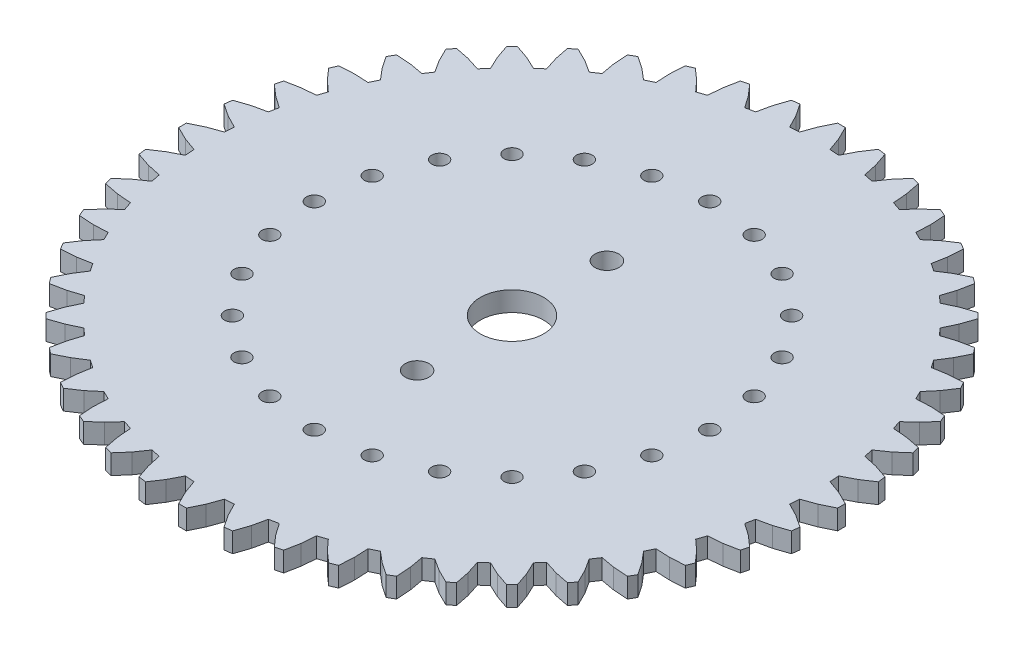
SolidWorks part; units mm, degrees
material "Plain Carbon Steel"
ref_plane "Front Plane" through (0, 0, 0) normal (0, 0, 1) x (1, 0, 0)
ref_plane "Top Plane" through (0, 0, 0) normal (0, 1, 0) x (1, 0, 0)
ref_plane "Right Plane" through (0, 0, 0) normal (1, 0, 0) x (0, 0, -1)
sketch "Sketch5" plane through (0, 0, 0) normal (0, 1, 0) x (1, 0, 0)
  line L0 (87.3464, 51.4964) -> (89.0397, 50.8872)
  line L1 (89.0397, 50.8872) -> (90.7249, 50.062)
  line L2 (90.7249, 50.062) -> (90.7249, 49.095)
  line L3 (90.7249, 49.095) -> (89.0397, 48.2698)
  line L4 (89.0397, 48.2698) -> (87.3464, 47.6606)
  line L5 (87.3464, 47.6606) -> (87.2693, 46.4828)
  line L6 (87.2693, 46.4828) -> (88.8685, 45.6578)
  line L7 (88.8685, 45.6578) -> (90.4317, 44.6196)
  line L8 (90.4317, 44.6196) -> (90.3054, 43.6609)
  line L9 (90.3054, 43.6609) -> (88.5268, 43.0627)
  line L10 (88.5268, 43.0627) -> (86.7686, 42.6797)
  line L11 (86.7686, 42.6797) -> (86.5383, 41.5221)
  line L12 (86.5383, 41.5221) -> (88.0162, 40.4955)
  line L13 (88.0162, 40.4955) -> (89.4304, 39.2621)
  line L14 (89.4304, 39.2621) -> (89.1801, 38.328)
  line L15 (89.1801, 38.328) -> (87.3386, 37.9672)
  line L16 (87.3386, 37.9672) -> (85.5454, 37.8169)
  line L17 (85.5454, 37.8169) -> (85.1661, 36.6994)
  line L18 (85.1661, 36.6994) -> (86.4974, 35.4884)
  line L19 (86.4974, 35.4884) -> (87.7385, 34.0811)
  line L20 (87.7385, 34.0811) -> (87.3685, 33.1877)
  line L21 (87.3685, 33.1877) -> (85.4956, 33.0702)
  line L22 (85.4956, 33.0702) -> (83.6981, 33.1553)
  line L23 (83.6981, 33.1553) -> (83.1762, 32.0968)
  line L24 (83.1762, 32.0968) -> (84.3379, 30.7226)
  line L25 (84.3379, 30.7226) -> (85.3848, 29.1653)
  line L26 (85.3848, 29.1653) -> (84.9013, 28.3278)
  line L27 (84.9013, 28.3278) -> (83.0292, 28.4557)
  line L28 (83.0292, 28.4557) -> (81.2581, 28.7747)
  line L29 (81.2581, 28.7747) -> (80.6024, 27.7935)
  line L30 (80.6024, 27.7935) -> (81.575, 26.2794)
  line L31 (81.575, 26.2794) -> (82.4096, 24.5987)
  line L32 (82.4096, 24.5987) -> (81.821, 23.8315)
  line L33 (81.821, 23.8315) -> (79.9815, 24.2028)
  line L34 (79.9815, 24.2028) -> (78.2673, 24.7502)
  line L35 (78.2673, 24.7502) -> (77.4891, 23.8628)
  line L36 (77.4891, 23.8628) -> (78.2556, 22.2348)
  line L37 (78.2556, 22.2348) -> (78.8638, 20.4595)
  line L38 (78.8638, 20.4595) -> (78.18, 19.7757)
  line L39 (78.18, 19.7757) -> (76.4047, 20.3839)
  line L40 (76.4047, 20.3839) -> (74.7767, 21.1504)
  line L41 (74.7767, 21.1504) -> (73.8893, 20.3722)
  line L42 (73.8893, 20.3722) -> (74.4368, 18.658)
  line L43 (74.4368, 18.658) -> (74.808, 16.8186)
  line L44 (74.808, 16.8186) -> (74.0408, 16.2299)
  line L45 (74.0408, 16.2299) -> (72.3602, 17.0645)
  line L46 (72.3602, 17.0645) -> (70.846, 18.0371)
  line L47 (70.846, 18.0371) -> (69.8648, 17.3814)
  line L48 (69.8648, 17.3814) -> (70.1838, 15.6104)
  line L49 (70.1838, 15.6104) -> (70.3117, 13.7382)
  line L50 (70.3117, 13.7382) -> (69.4742, 13.2547)
  line L51 (69.4742, 13.2547) -> (67.9169, 14.3016)
  line L52 (67.9169, 14.3016) -> (66.5427, 15.4634)
  line L53 (66.5427, 15.4634) -> (65.4842, 14.9415)
  line L54 (65.4842, 14.9415) -> (65.5693, 13.1439)
  line L55 (65.5693, 13.1439) -> (65.4518, 11.271)
  line L56 (65.4518, 11.271) -> (64.5584, 10.901)
  line L57 (64.5584, 10.901) -> (63.1511, 12.1422)
  line L58 (63.1511, 12.1422) -> (61.9401, 13.4734)
  line L59 (61.9401, 13.4734) -> (60.8226, 13.0941)
  line L60 (60.8226, 13.0941) -> (60.6724, 11.3009)
  line L61 (60.6724, 11.3009) -> (60.3115, 9.4594)
  line L62 (60.3115, 9.4594) -> (59.3774, 9.2091)
  line L63 (59.3774, 9.2091) -> (58.144, 10.6233)
  line L64 (58.144, 10.6233) -> (57.1174, 12.1012)
  line L65 (57.1174, 12.1012) -> (55.9598, 11.8709)
  line L66 (55.9598, 11.8709) -> (55.5768, 10.1127)
  line L67 (55.5768, 10.1127) -> (54.9786, 8.3341)
  line L68 (54.9786, 8.3341) -> (54.0199, 8.2078)
  line L69 (54.0199, 8.2078) -> (52.9817, 9.771)
  line L70 (52.9817, 9.771) -> (52.1567, 11.3702)
  line L71 (52.1567, 11.3702) -> (50.979, 11.2931)
  line L72 (50.979, 11.2931) -> (50.3698, 9.5998)
  line L73 (50.3698, 9.5998) -> (49.5446, 7.9146)
  line L74 (49.5446, 7.9146) -> (48.5775, 7.9146)
  line L75 (48.5775, 7.9146) -> (47.7523, 9.5998)
  line L76 (47.7523, 9.5998) -> (47.1431, 11.2931)
  line L77 (47.1431, 11.2931) -> (45.9654, 11.3702)
  line L78 (45.9654, 11.3702) -> (45.1403, 9.771)
  line L79 (45.1403, 9.771) -> (44.1021, 8.2078)
  line L80 (44.1021, 8.2078) -> (43.1434, 8.3341)
  line L81 (43.1434, 8.3341) -> (42.5452, 10.1127)
  line L82 (42.5452, 10.1127) -> (42.1622, 11.8709)
  line L83 (42.1622, 11.8709) -> (41.0046, 12.1012)
  line L84 (41.0046, 12.1012) -> (39.978, 10.6233)
  line L85 (39.978, 10.6233) -> (38.7447, 9.2091)
  line L86 (38.7447, 9.2091) -> (37.8106, 9.4594)
  line L87 (37.8106, 9.4594) -> (37.4497, 11.3009)
  line L88 (37.4497, 11.3009) -> (37.2994, 13.0941)
  line L89 (37.2994, 13.0941) -> (36.1819, 13.4734)
  line L90 (36.1819, 13.4734) -> (34.9709, 12.1422)
  line L91 (34.9709, 12.1422) -> (33.5636, 10.901)
  line L92 (33.5636, 10.901) -> (32.6702, 11.271)
  line L93 (32.6702, 11.271) -> (32.5527, 13.1439)
  line L94 (32.5527, 13.1439) -> (32.6378, 14.9415)
  line L95 (32.6378, 14.9415) -> (31.5793, 15.4634)
  line L96 (31.5793, 15.4634) -> (30.2051, 14.3016)
  line L97 (30.2051, 14.3016) -> (28.6478, 13.2547)
  line L98 (28.6478, 13.2547) -> (27.8103, 13.7382)
  line L99 (27.8103, 13.7382) -> (27.9382, 15.6104)
  line L100 (27.9382, 15.6104) -> (28.2572, 17.3814)
  line L101 (28.2572, 17.3814) -> (27.276, 18.0371)
  line L102 (27.276, 18.0371) -> (25.7619, 17.0645)
  line L103 (25.7619, 17.0645) -> (24.0812, 16.2299)
  line L104 (24.0812, 16.2299) -> (23.314, 16.8186)
  line L105 (23.314, 16.8186) -> (23.6853, 18.658)
  line L106 (23.6853, 18.658) -> (24.2327, 20.3722)
  line L107 (24.2327, 20.3722) -> (23.3453, 21.1504)
  line L108 (23.3453, 21.1504) -> (21.7173, 20.3839)
  line L109 (21.7173, 20.3839) -> (19.9421, 19.7757)
  line L110 (19.9421, 19.7757) -> (19.2582, 20.4595)
  line L111 (19.2582, 20.4595) -> (19.8664, 22.2348)
  line L112 (19.8664, 22.2348) -> (20.6329, 23.8628)
  line L113 (20.6329, 23.8628) -> (19.8547, 24.7502)
  line L114 (19.8547, 24.7502) -> (18.1405, 24.2028)
  line L115 (18.1405, 24.2028) -> (16.3011, 23.8315)
  line L116 (16.3011, 23.8315) -> (15.7124, 24.5987)
  line L117 (15.7124, 24.5987) -> (16.547, 26.2794)
  line L118 (16.547, 26.2794) -> (17.5196, 27.7935)
  line L119 (17.5196, 27.7935) -> (16.8639, 28.7747)
  line L120 (16.8639, 28.7747) -> (15.0929, 28.4557)
  line L121 (15.0929, 28.4557) -> (13.2207, 28.3278)
  line L122 (13.2207, 28.3278) -> (12.7372, 29.1653)
  line L123 (12.7372, 29.1653) -> (13.7841, 30.7226)
  line L124 (13.7841, 30.7226) -> (14.9459, 32.0968)
  line L125 (14.9459, 32.0968) -> (14.424, 33.1553)
  line L126 (14.424, 33.1553) -> (12.6264, 33.0702)
  line L127 (12.6264, 33.0702) -> (10.7535, 33.1877)
  line L128 (10.7535, 33.1877) -> (10.3835, 34.0811)
  line L129 (10.3835, 34.0811) -> (11.6247, 35.4884)
  line L130 (11.6247, 35.4884) -> (12.9559, 36.6994)
  line L131 (12.9559, 36.6994) -> (12.5766, 37.8169)
  line L132 (12.5766, 37.8169) -> (10.7834, 37.9672)
  line L133 (10.7834, 37.9672) -> (8.9419, 38.328)
  line L134 (8.9419, 38.328) -> (8.6916, 39.2621)
  line L135 (8.6916, 39.2621) -> (10.1058, 40.4955)
  line L136 (10.1058, 40.4955) -> (11.5837, 41.5221)
  line L137 (11.5837, 41.5221) -> (11.3534, 42.6797)
  line L138 (11.3534, 42.6797) -> (9.5952, 43.0627)
  line L139 (9.5952, 43.0627) -> (7.8167, 43.6609)
  line L140 (7.8167, 43.6609) -> (7.6903, 44.6196)
  line L141 (7.6903, 44.6196) -> (9.2536, 45.6578)
  line L142 (9.2536, 45.6578) -> (10.8528, 46.4828)
  line L143 (10.8528, 46.4828) -> (10.7757, 47.6606)
  line L144 (10.7757, 47.6606) -> (9.0823, 48.2698)
  line L145 (9.0823, 48.2698) -> (7.3971, 49.095)
  line L146 (7.3971, 49.095) -> (7.3971, 50.062)
  line L147 (7.3971, 50.062) -> (9.0823, 50.8872)
  line L148 (9.0823, 50.8872) -> (10.7757, 51.4964)
  line L149 (10.7757, 51.4964) -> (10.8528, 52.6742)
  line L150 (10.8528, 52.6742) -> (9.2536, 53.4992)
  line L151 (9.2536, 53.4992) -> (7.6903, 54.5374)
  line L152 (7.6903, 54.5374) -> (7.8167, 55.4961)
  line L153 (7.8167, 55.4961) -> (9.5952, 56.0943)
  line L154 (9.5952, 56.0943) -> (11.3534, 56.4773)
  line L155 (11.3534, 56.4773) -> (11.5837, 57.6349)
  line L156 (11.5837, 57.6349) -> (10.1058, 58.6615)
  line L157 (10.1058, 58.6615) -> (8.6916, 59.8949)
  line L158 (8.6916, 59.8949) -> (8.9419, 60.829)
  line L159 (8.9419, 60.829) -> (10.7834, 61.1898)
  line L160 (10.7834, 61.1898) -> (12.5766, 61.3401)
  line L161 (12.5766, 61.3401) -> (12.9559, 62.4576)
  line L162 (12.9559, 62.4576) -> (11.6247, 63.6686)
  line L163 (11.6247, 63.6686) -> (10.3835, 65.0759)
  line L164 (10.3835, 65.0759) -> (10.7535, 65.9693)
  line L165 (10.7535, 65.9693) -> (12.6264, 66.0868)
  line L166 (12.6264, 66.0868) -> (14.424, 66.0017)
  line L167 (14.424, 66.0017) -> (14.9459, 67.0602)
  line L168 (14.9459, 67.0602) -> (13.7841, 68.4344)
  line L169 (13.7841, 68.4344) -> (12.7372, 69.9917)
  line L170 (12.7372, 69.9917) -> (13.2207, 70.8292)
  line L171 (13.2207, 70.8292) -> (15.0929, 70.7013)
  line L172 (15.0929, 70.7013) -> (16.8639, 70.3823)
  line L173 (16.8639, 70.3823) -> (17.5196, 71.3635)
  line L174 (17.5196, 71.3635) -> (16.547, 72.8776)
  line L175 (16.547, 72.8776) -> (15.7124, 74.5583)
  line L176 (15.7124, 74.5583) -> (16.3011, 75.3255)
  line L177 (16.3011, 75.3255) -> (18.1405, 74.9542)
  line L178 (18.1405, 74.9542) -> (19.8547, 74.4068)
  line L179 (19.8547, 74.4068) -> (20.6329, 75.2942)
  line L180 (20.6329, 75.2942) -> (19.8664, 76.9222)
  line L181 (19.8664, 76.9222) -> (19.2582, 78.6975)
  line L182 (19.2582, 78.6975) -> (19.9421, 79.3813)
  line L183 (19.9421, 79.3813) -> (21.7173, 78.7731)
  line L184 (21.7173, 78.7731) -> (23.3453, 78.0066)
  line L185 (23.3453, 78.0066) -> (24.2327, 78.7848)
  line L186 (24.2327, 78.7848) -> (23.6853, 80.499)
  line L187 (23.6853, 80.499) -> (23.314, 82.3384)
  line L188 (23.314, 82.3384) -> (24.0812, 82.9271)
  line L189 (24.0812, 82.9271) -> (25.7619, 82.0925)
  line L190 (25.7619, 82.0925) -> (27.276, 81.1199)
  line L191 (27.276, 81.1199) -> (28.2572, 81.7756)
  line L192 (28.2572, 81.7756) -> (27.9382, 83.5466)
  line L193 (27.9382, 83.5466) -> (27.8103, 85.4188)
  line L194 (27.8103, 85.4188) -> (28.6478, 85.9023)
  line L195 (28.6478, 85.9023) -> (30.2051, 84.8554)
  line L196 (30.2051, 84.8554) -> (31.5793, 83.6936)
  line L197 (31.5793, 83.6936) -> (32.6378, 84.2155)
  line L198 (32.6378, 84.2155) -> (32.5527, 86.0131)
  line L199 (32.5527, 86.0131) -> (32.6702, 87.886)
  line L200 (32.6702, 87.886) -> (33.5636, 88.256)
  line L201 (33.5636, 88.256) -> (34.9709, 87.0148)
  line L202 (34.9709, 87.0148) -> (36.1819, 85.6836)
  line L203 (36.1819, 85.6836) -> (37.2994, 86.0629)
  line L204 (37.2994, 86.0629) -> (37.4497, 87.8561)
  line L205 (37.4497, 87.8561) -> (37.8106, 89.6976)
  line L206 (37.8106, 89.6976) -> (38.7447, 89.9479)
  line L207 (38.7447, 89.9479) -> (39.978, 88.5337)
  line L208 (39.978, 88.5337) -> (41.0046, 87.0558)
  line L209 (41.0046, 87.0558) -> (42.1622, 87.2861)
  line L210 (42.1622, 87.2861) -> (42.5452, 89.0443)
  line L211 (42.5452, 89.0443) -> (43.1434, 90.8228)
  line L212 (43.1434, 90.8228) -> (44.1021, 90.9492)
  line L213 (44.1021, 90.9492) -> (45.1403, 89.386)
  line L214 (45.1403, 89.386) -> (45.9654, 87.7868)
  line L215 (45.9654, 87.7868) -> (47.1431, 87.8639)
  line L216 (47.1431, 87.8639) -> (47.7523, 89.5572)
  line L217 (47.7523, 89.5572) -> (48.5775, 91.2424)
  line L218 (48.5775, 91.2424) -> (49.5446, 91.2424)
  line L219 (49.5446, 91.2424) -> (50.3698, 89.5572)
  line L220 (50.3698, 89.5572) -> (50.979, 87.8639)
  line L221 (50.979, 87.8639) -> (52.1567, 87.7868)
  line L222 (52.1567, 87.7868) -> (52.9817, 89.386)
  line L223 (52.9817, 89.386) -> (54.0199, 90.9492)
  line L224 (54.0199, 90.9492) -> (54.9786, 90.8228)
  line L225 (54.9786, 90.8228) -> (55.5768, 89.0443)
  line L226 (55.5768, 89.0443) -> (55.9598, 87.2861)
  line L227 (55.9598, 87.2861) -> (57.1174, 87.0558)
  line L228 (57.1174, 87.0558) -> (58.144, 88.5337)
  line L229 (58.144, 88.5337) -> (59.3774, 89.9479)
  line L230 (59.3774, 89.9479) -> (60.3115, 89.6976)
  line L231 (60.3115, 89.6976) -> (60.6724, 87.8561)
  line L232 (60.6724, 87.8561) -> (60.8226, 86.0629)
  line L233 (60.8226, 86.0629) -> (61.9401, 85.6836)
  line L234 (61.9401, 85.6836) -> (63.1511, 87.0148)
  line L235 (63.1511, 87.0148) -> (64.5584, 88.256)
  line L236 (64.5584, 88.256) -> (65.4518, 87.886)
  line L237 (65.4518, 87.886) -> (65.5693, 86.0131)
  line L238 (65.5693, 86.0131) -> (65.4842, 84.2155)
  line L239 (65.4842, 84.2155) -> (66.5427, 83.6936)
  line L240 (66.5427, 83.6936) -> (67.9169, 84.8554)
  line L241 (67.9169, 84.8554) -> (69.4742, 85.9023)
  line L242 (69.4742, 85.9023) -> (70.3117, 85.4188)
  line L243 (70.3117, 85.4188) -> (70.1838, 83.5466)
  line L244 (70.1838, 83.5466) -> (69.8648, 81.7756)
  line L245 (69.8648, 81.7756) -> (70.846, 81.1199)
  line L246 (70.846, 81.1199) -> (72.3602, 82.0925)
  line L247 (72.3602, 82.0925) -> (74.0408, 82.9271)
  line L248 (74.0408, 82.9271) -> (74.808, 82.3384)
  line L249 (74.808, 82.3384) -> (74.4368, 80.499)
  line L250 (74.4368, 80.499) -> (73.8893, 78.7848)
  line L251 (73.8893, 78.7848) -> (74.7767, 78.0066)
  line L252 (74.7767, 78.0066) -> (76.4047, 78.7731)
  line L253 (76.4047, 78.7731) -> (78.18, 79.3813)
  line L254 (78.18, 79.3813) -> (78.8638, 78.6975)
  line L255 (78.8638, 78.6975) -> (78.2556, 76.9222)
  line L256 (78.2556, 76.9222) -> (77.4891, 75.2942)
  line L257 (77.4891, 75.2942) -> (78.2673, 74.4068)
  line L258 (78.2673, 74.4068) -> (79.9815, 74.9542)
  line L259 (79.9815, 74.9542) -> (81.821, 75.3255)
  line L260 (81.821, 75.3255) -> (82.4096, 74.5583)
  line L261 (82.4096, 74.5583) -> (81.575, 72.8776)
  line L262 (81.575, 72.8776) -> (80.6024, 71.3635)
  line L263 (80.6024, 71.3635) -> (81.2581, 70.3823)
  line L264 (81.2581, 70.3823) -> (83.0292, 70.7013)
  line L265 (83.0292, 70.7013) -> (84.9013, 70.8292)
  line L266 (84.9013, 70.8292) -> (85.3848, 69.9917)
  line L267 (85.3848, 69.9917) -> (84.3379, 68.4344)
  line L268 (84.3379, 68.4344) -> (83.1762, 67.0602)
  line L269 (83.1762, 67.0602) -> (83.6981, 66.0017)
  line L270 (83.6981, 66.0017) -> (85.4956, 66.0868)
  line L271 (85.4956, 66.0868) -> (87.3685, 65.9693)
  line L272 (87.3685, 65.9693) -> (87.7385, 65.0759)
  line L273 (87.7385, 65.0759) -> (86.4974, 63.6686)
  line L274 (86.4974, 63.6686) -> (85.1661, 62.4576)
  line L275 (85.1661, 62.4576) -> (85.5454, 61.3401)
  line L276 (85.5454, 61.3401) -> (87.3386, 61.1898)
  line L277 (87.3386, 61.1898) -> (89.1801, 60.829)
  line L278 (89.1801, 60.829) -> (89.4304, 59.8949)
  line L279 (89.4304, 59.8949) -> (88.0162, 58.6615)
  line L280 (88.0162, 58.6615) -> (86.5383, 57.6349)
  line L281 (86.5383, 57.6349) -> (86.7686, 56.4773)
  line L282 (86.7686, 56.4773) -> (88.5268, 56.0943)
  line L283 (88.5268, 56.0943) -> (90.3054, 55.4961)
  line L284 (90.3054, 55.4961) -> (90.4317, 54.5374)
  line L285 (90.4317, 54.5374) -> (88.8685, 53.4992)
  line L286 (88.8685, 53.4992) -> (87.2693, 52.6742)
  line L287 (87.2693, 52.6742) -> (87.3464, 51.4964)
  line L288 (49.061, 91.2424) -> (49.061, 7.9146) construction
  line L289 (7.3971, 49.5785) -> (90.7249, 49.5785) construction
  point P292 (49.061, 49.5785)
sketch "Sketch6" plane through (0, 0, 0) normal (0, 1, 0) x (1, 0, 0)
  line L0 (49.061, 91.2424) -> (49.061, 7.9146) construction
  circle A0 centre (49.061, 49.5785) radius 4
  dimension "D1" = 8
sketch "Sketch7" plane through (0, 0, 0) normal (0, 1, 0) x (1, 0, 0)
  line L0 (49.061, 91.2424) -> (49.061, 7.9146) construction
  line L1 (25.4921, 49.5785) -> (64.6594, 49.5785) construction
  line L2 (7.3971, 49.5785) -> (90.7249, 49.5785) construction
  circle A0 centre (49.061, 61.5785) radius 1.5
  circle A1 centre (49.061, 37.5785) radius 1.5
  dimension "D2" = 3
  dimension "D1" = 12
sketch "Sketch8" plane through (0, 0, 0) normal (0, 1, 0) x (1, 0, 0)
  line L0 (7.3971, 49.5785) -> (90.7249, 49.5785) construction
  circle A0 centre (49.061, 49.5785) radius 27
  dimension "D1" = 54
sketch "Sketch9" plane through (0, 0, 0) normal (0, 1, 0) x (1, 0, 0)
  line L0 (49.061, 91.2424) -> (49.061, 7.9146) construction
  line L1 (49.061, 74.5785) -> (49.061, 76.5785) construction
  circle A0 centre (49.061, 74.5785) radius 1
  circle A1 centre (49.061, 49.5785) radius 27 construction
  circle A2 centre (55.5315, 73.7266) radius 1
  circle A3 centre (61.561, 71.2291) radius 1
  circle A4 centre (66.7387, 67.2562) radius 1
  circle A5 centre (70.7116, 62.0785) radius 1
  circle A6 centre (73.2092, 56.049) radius 1
  circle A7 centre (74.061, 49.5785) radius 1
  circle A8 centre (73.2092, 43.108) radius 1
  circle A9 centre (70.7116, 37.0785) radius 1
  circle A10 centre (66.7387, 31.9008) radius 1
  circle A11 centre (61.561, 27.9279) radius 1
  circle A12 centre (55.5315, 25.4304) radius 1
  circle A13 centre (49.061, 24.5785) radius 1
  circle A14 centre (42.5905, 25.4304) radius 1
  circle A15 centre (36.561, 27.9279) radius 1
  circle A16 centre (31.3833, 31.9008) radius 1
  circle A17 centre (27.4104, 37.0785) radius 1
  circle A18 centre (24.9129, 43.108) radius 1
  circle A19 centre (24.061, 49.5785) radius 1
  circle A20 centre (24.9129, 56.049) radius 1
  circle A21 centre (27.4104, 62.0785) radius 1
  circle A22 centre (31.3833, 67.2562) radius 1
  circle A23 centre (36.561, 71.2291) radius 1
  circle A24 centre (42.5905, 73.7266) radius 1
  point P55 (49.061, 49.5785)
  dimension "D1" = 2
  dimension "D2" = 2
  dimension "D3" = 24
extrude "Boss-Extrude1" add sketch "Sketch8" along normal blind 2.5
extrude "Boss-Extrude2" add sketch "Sketch5" along normal up to surface (2.5 mm away) up to face at (49.061, 2.5, -22.5785)
extrude "Cut-Extrude1" cut sketch "Sketch6" along normal up to next
extrude "Cut-Extrude2" cut sketch "Sketch7" along normal blind 2.5
extrude "Cut-Extrude3" cut sketch "Sketch9" along normal blind 2.5
ref_axis "Axis1" through (49.061, 2.5, -49.5785) along (0, -1, 0)
